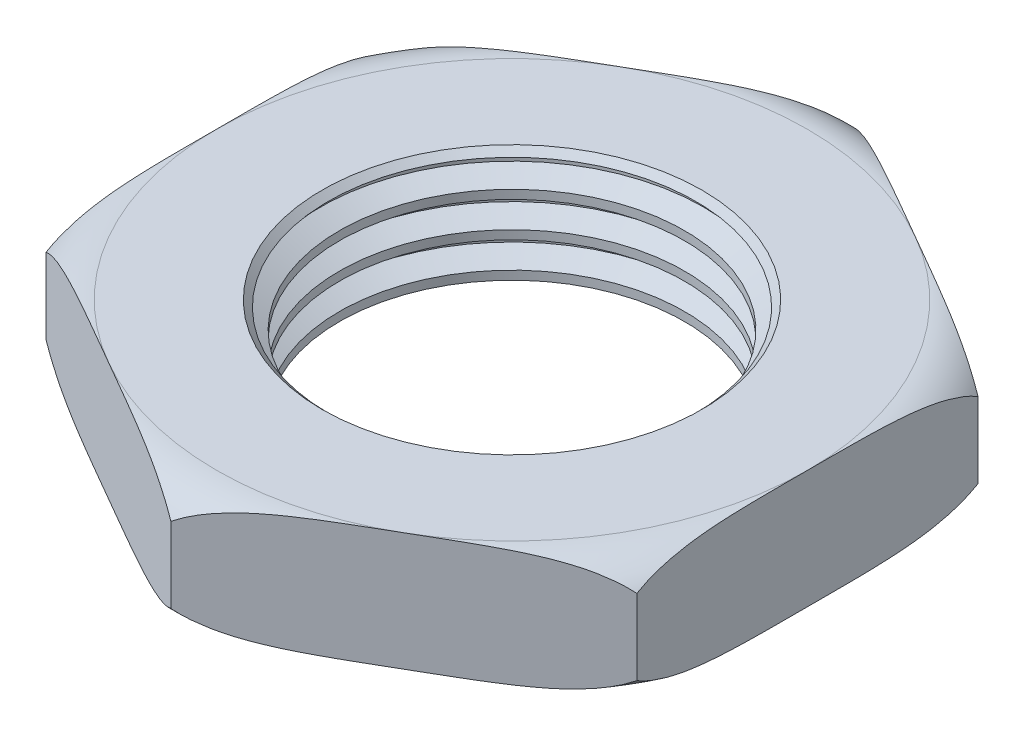
SolidWorks part; units mm, degrees
ref_plane "Front" through (0, 0, 0) normal (0, 0, 1) x (1, 0, 0)
ref_plane "Top" through (0, 0, 0) normal (0, 1, 0) x (1, 0, 0)
ref_plane "Right" through (0, 0, 0) normal (1, 0, 0) x (0, 0, -1)
sketch "Sketch1" plane through (0, 0, 0) normal (0, 1, 0) x (1, 0, 0)
  line L1 (0, 9.1654) -> (-7.9375, 4.5827)
  line L2 (-7.9375, 4.5827) -> (-7.9375, -4.5827)
  line L3 (-7.9375, -4.5827) -> (0, -9.1654)
  line L4 (0, -9.1654) -> (7.9375, -4.5827)
  line L5 (7.9375, -4.5827) -> (7.9375, 4.5827)
  line L6 (7.9375, 4.5827) -> (0, 9.1654)
  circle A0 centre (0, 0) radius 7.9375 construction
  dimension "Hex Flats" = 15.875
extrude "Extrude1" add sketch "Sketch1" along normal blind 3.175
ref_axis "Axis1" through (0, 3.9852, 0) along (0, -1, 0)
sketch "Sketch2" plane through (0, 0, 0) normal (0, 0, 1) x (1, 0, 0)
  line L0 (0, 1.6636) -> (0, -0.3796) construction
  line L1 (0, 3.175) -> (4.6343, 3.175)
  line L2 (0, 3.175) -> (7.9375, 3.175) construction
  line L4 (0, 2.2343) -> (4.6343, 2.2343)
  line L5 (4.6343, 3.175) -> (5.1435, 2.881)
  line L6 (5.1435, 2.881) -> (5.1435, 2.7634)
  line L7 (5.1435, 2.7634) -> (4.6343, 2.4694)
  line L9 (4.6343, 2.2343) -> (4.6343, 2.4694)
  line L10 (0, 2.2343) -> (0, 3.175)
  line L11 (4.6343, 3.175) -> (4.6343, 2.4694) construction
  line L12 (5.1435, 2.8222) -> (4.6343, 2.8222) construction
  dimension "D1" = 60
  dimension "D2" = 0.2352
  dimension "D5" = 0.1176
  dimension "Pitch" = 0.9407
  dimension "Major Dia." = 10.287
revolve "Cut-Revolve1" cut sketch "Sketch2" angle 360 about L0
pattern_linear "LPattern2" count 4 spacing 0.9407 along (0, -1, 0) of "Cut-Revolve1"
chamfer "Chamfer1" distance 0.4704 angle 45 1 edges at (0, 3.175, 4.6343) first distance on face at (0, 3.175, 0)
sketch "Sketch3" plane through (0, 0, 0) normal (1, 0, 0) x (0, 0, -1)
  line L0 (0, 3.9198) -> (0, -0.7448) construction
  line L1 (7.9375, 3.175) -> (9.1654, 3.175)
  line L2 (4.5827, 3.175) -> (9.1654, 3.175) construction
  line L3 (9.1654, 3.175) -> (9.1654, 2.6024)
  line L4 (9.1654, 3.175) -> (9.1654, 0) construction
  line L5 (7.9375, 3.175) -> (9.1654, 2.6024) construction
  line L6 (9.1654, 1.5875) -> (0, 1.5875) construction
  line L7 (9.1654, 0) -> (9.1654, 0.5726)
  line L8 (7.9375, 0) -> (9.1654, 0)
  arc A0 (9.1654, 2.6024) -> (7.9375, 3.175) centre (7.9375, 1.572) ccw
  arc A1 (9.1654, 0.5726) -> (7.9375, 0) centre (7.9375, 1.603) cw
  dimension "D1" = 25
  dimension "D2" = 15.875
revolve "Cut-Revolve2" cut sketch "Sketch3" angle 360 about L0
equation "\"D5@Sketch2\"=\"Pitch@Sketch2\"/8"
equation "\"D2@Sketch2\"=\"Pitch@Sketch2\"/4"
equation "\"D3@LPattern2\"=\"Pitch@Sketch2\""
equation "\"D1@LPattern2\"=int(\"Height@Extrude1\"/\"Pitch@Sketch2\")+1"
equation "\"D1@Chamfer1\"=\"Pitch@Sketch2\"/2"
equation "\"D2@Sketch3\"=\"Hex Flats@Sketch1\""
